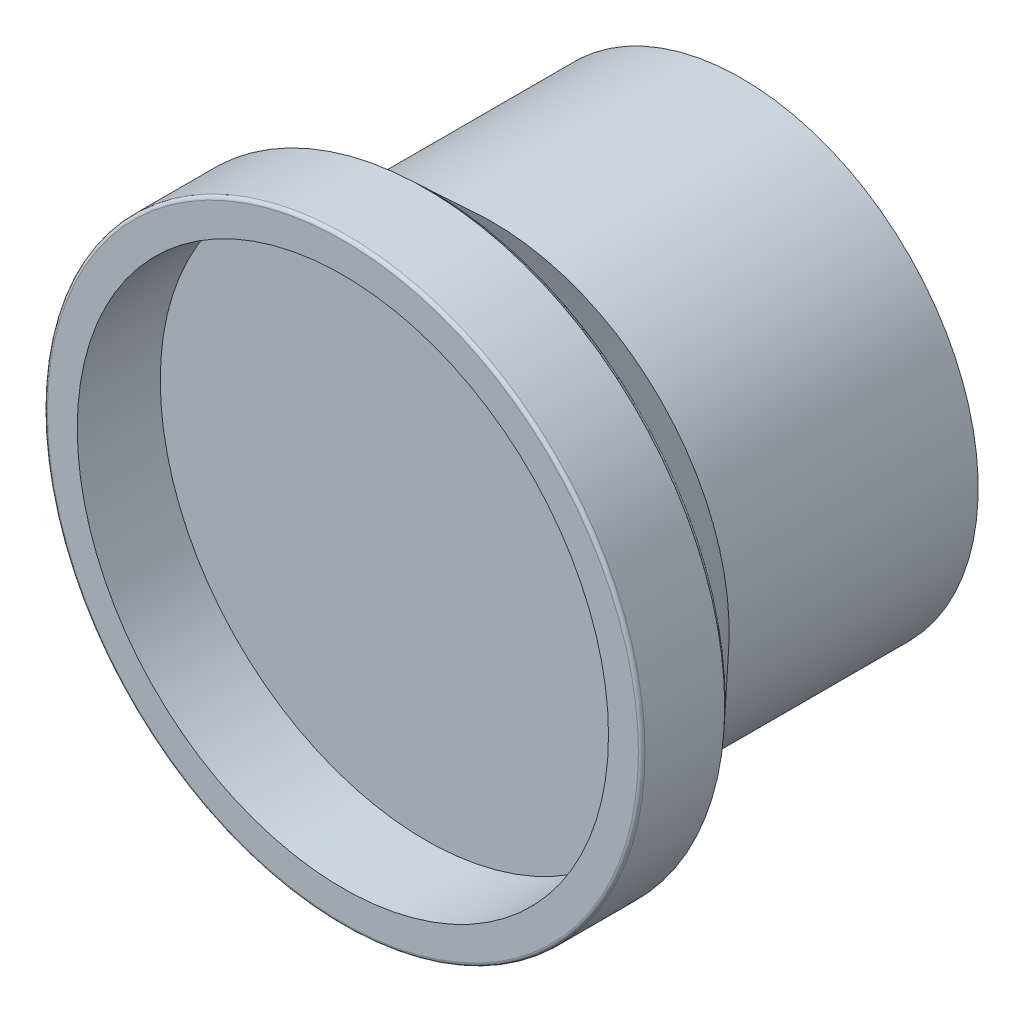
SolidWorks part; units mm, degrees
material "6061 Alloy"
ref_plane "Front" through (0, 0, 0) normal (0, 0, 1) x (1, 0, 0)
ref_plane "Top" through (0, 0, 0) normal (0, 1, 0) x (1, 0, 0)
ref_plane "Right" through (0, 0, 0) normal (1, 0, 0) x (0, 0, -1)
sketch "Sketch2" plane through (0, 0, 0) normal (0, 0, 1) x (1, 0, 0)
  circle A0 centre (0, 0) radius 900
  circle A1 centre (0, 0) radius 800
  dimension "D1" = 1800
  dimension "D2" = 1600
extrude "Boss-Extrude1" add sketch "Sketch2" along normal blind 250
sketch "Sketch3" plane through (0, 0, 0) normal (1, 0, 0) x (0, 0, -1)
  line L0 (0, 0) -> (200.7054, 0)
  line L1 (247.888, 0) -> (-247.888, 0) construction
  line L5 (0, 0) -> (0, -900)
  line L6 (0, -900) -> (200.7054, -712.6876)
  line L7 (200.7054, 0) -> (200.7054, -712.6876)
revolve "Revolve1" add sketch "Sketch3" angle 360 about L0
fillet "Fillet2" radius 10 1 edges at (900, 0, 250)
fillet "Fillet3" radius 10 1 edges at (900, 0, 0)
sketch "Sketch4" plane through (0, 0, -200.7054) normal (0, 0, -1) x (-1, 0, 0)
  circle A0 centre (0, 0) radius 712.6876
  circle A1 centre (0, 0) radius 600
  dimension "D1" = 1425.3752
  dimension "D2" = 1200
extrude "Boss-Extrude2" add sketch "Sketch4" along normal blind 750
sketch "Sketch5" plane through (0, 0, -200.7054) normal (0, 0, -1) x (-1, 0, 0)
  circle A0 centre (0, 0) radius 600
  dimension "D1" = 1200
extrude "Boss-Extrude3" add sketch "Sketch5" along normal blind 700
